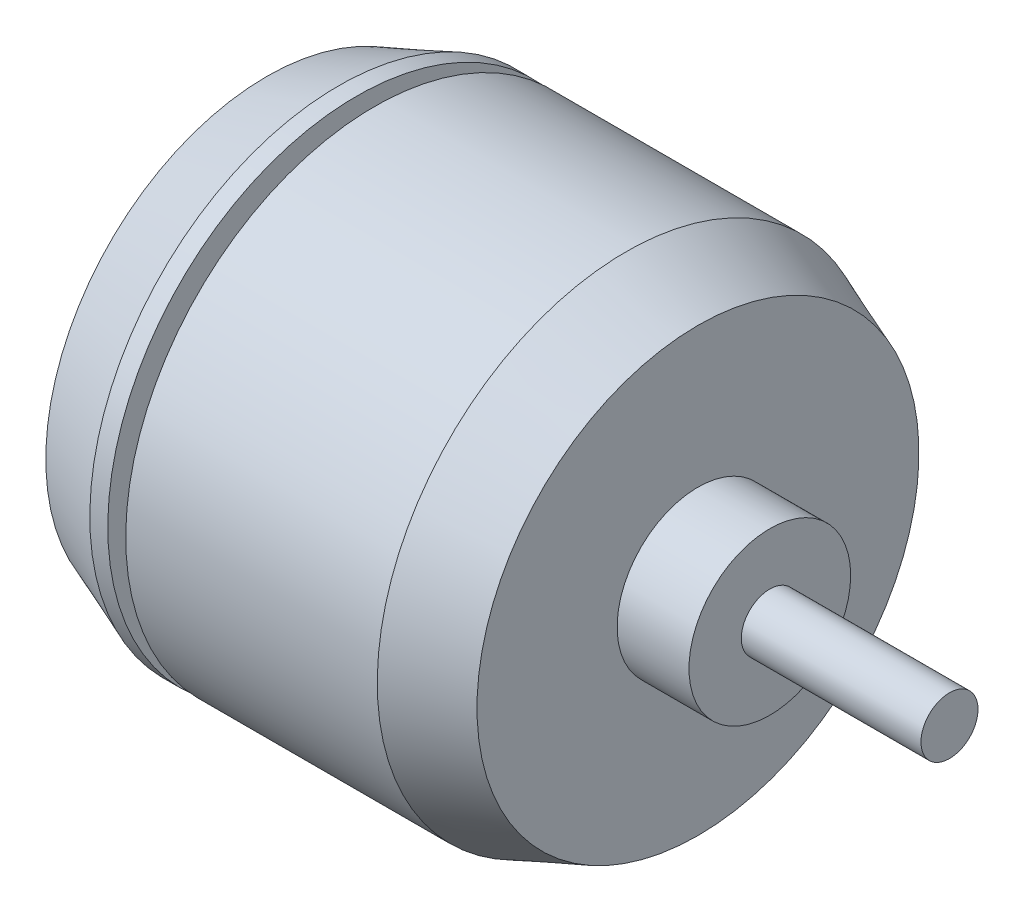
SolidWorks part; units mm, degrees
ref_plane "Front Plane" through (0, 0, 0) normal (0, 0, 1) x (1, 0, 0)
ref_plane "Top Plane" through (0, 0, 0) normal (0, 1, 0) x (1, 0, 0)
ref_plane "Right Plane" through (0, 0, 0) normal (1, 0, 0) x (0, 0, -1)
sketch "Sketch1" plane through (0, 0, 0) normal (1, 0, 0) x (0, 0, -1)
  circle A0 centre (0, 0) radius 13.85
  dimension "D1" = 27.7
extrude "Boss-Extrude1" add sketch "Sketch1" along normal mid plane 24
sketch "Sketch2" plane through (12, 0, 0) normal (1, 0, 0) x (0, 0, -1)
  circle A0 centre (0, 0) radius 4.5
  dimension "D1" = 9
extrude "Boss-Extrude2" add sketch "Sketch2" along normal blind 4
sketch "Sketch3" plane through (16, 0, 0) normal (1, 0, 0) x (0, 0, -1)
  circle A0 centre (0, 0) radius 1.5875
  dimension "D1" = 3.175
extrude "Boss-Extrude3" add sketch "Sketch3" along normal blind 10
sketch "Sketch4" plane through (0, 0, 0) normal (0, 0, 1) x (1, 0, 0)
  line L0 (-12, 12.3) -> (-8, 13.85)
  line L1 (-12, 13.85) -> (-12, -13.85) construction
  line L2 (12, 13.85) -> (-12, 13.85) construction
  line L3 (-12, 12.3) -> (-12, 13.85)
  line L4 (-7, 13.85) -> (-6, 13.85)
  line L5 (-7, 13.85) -> (-7, 4)
  line L6 (-7, 4) -> (-6, 4)
  line L7 (-6, 13.85) -> (-6, 4)
  line L8 (-12, 13.85) -> (-8, 13.85)
  line L9 (0, 0) -> (0, 13.85) construction
  line L10 (12, 13.85) -> (8, 13.85)
  line L11 (12, 12.3) -> (8, 13.85)
  line L12 (12, 12.3) -> (12, 13.85)
  line L13 (0, 0) -> (26, 0) construction
  line L14 (26, -1.5875) -> (26, 1.5875) construction
  dimension "D1" = 12.3
  dimension "D2" = 6
  dimension "D3" = 1
  dimension "D4" = 1
  dimension "D5" = 4
revolve "Cut-Revolve1" cut sketch "Sketch4" angle 360 about L13
sketch "Sketch5" plane through (-12, 0, 0) normal (-1, 0, 0) x (0, 0, 1)
  line L0 (0, 0) -> (0, 8) construction
  line L1 (0, 0) -> (9.5, 0) construction
  line L2 (-5.6569, 5.6569) -> (0, 0) construction
  circle A0 centre (-5.6569, 5.6569) radius 2.5
  circle A1 centre (5.6569, 5.6569) radius 2.5
  circle A2 centre (5.6569, -5.6569) radius 2.5
  circle A3 centre (-5.6569, -5.6569) radius 2.5
  point P0 (0, 8)
  point P1 (9.5, 0)
  point P5 (-9.5, 0)
  point P7 (0, -8)
  point P19 (0, 0)
  dimension "D4" = 5
  dimension "D1" = 8
  dimension "D2" = 9.5
  dimension "D3" = 45
  dimension "D5" = 8
  dimension "D6" = 4
extrude "Cut-Extrude1" cut sketch "Sketch5" against normal up to next
hole_wizard "M3x0.5 Tapped Hole1" positions "Sketch6" profile "Sketch7" tap size "M3x0.5" standard "ANSI Metric" end condition up to next
sketch "Sketch6" plane through (-12, 0, 0) normal (-1, 0, 0) x (0, 0, 1)
  point P0 (0, 8)
  point P3 (9.5, 0)
  point P6 (0, -8)
  point P9 (-9.5, 0)
sketch "Sketch7" plane through (-12, 8, 0) normal (0, 1, 0) x (0, 0, 1)
  line L0 (0, 0) -> (0, 5)
  line L1 (0, 5) -> (1.25, 5)
  line L2 (1.25, 5) -> (1.25, 0)
  line L5 (1.25, 0) -> (0, 0)
  line L11 (0, -6.35) -> (0, 107.95) construction
  dimension "Thru Tap Drill Dia." = 2.5
  dimension "Thru Tap Drill Depth" = 5
cosmetic thread "Hole Thread1" parameters "D2"=3
cosmetic thread "Hole Thread2" parameters "D2"=3
cosmetic thread "Hole Thread3" parameters "D2"=3
cosmetic thread "Hole Thread4" parameters "D2"=3
sketch "Sketch8" plane through (-12, 0, 0) normal (-1, 0, 0) x (0, 0, 1)
  circle A0 centre (0, 0) radius 2
  dimension "D1" = 4
extrude "Boss-Extrude4" add sketch "Sketch8" along normal blind 2
equation "\"D1@Sketch3\"=0.125in"
